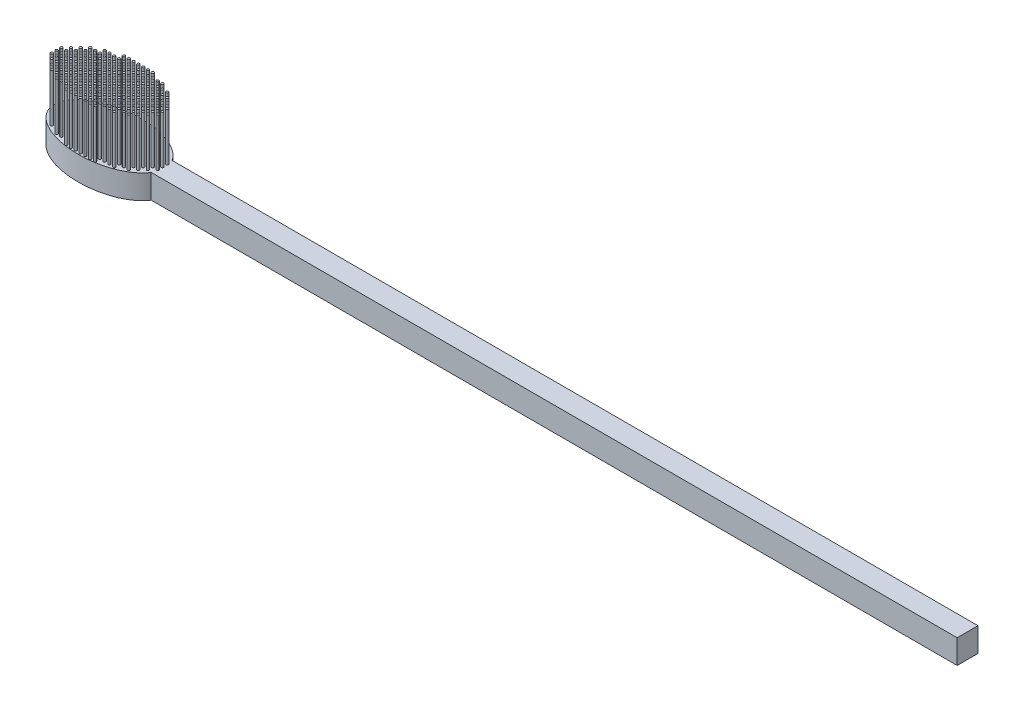
SolidWorks part; units mm, degrees
ref_plane "Front Plane" through (0, 0, 0) normal (0, 0, 1) x (1, 0, 0)
ref_plane "Top Plane" through (0, 0, 0) normal (0, 1, 0) x (1, 0, 0)
ref_plane "Right Plane" through (0, 0, 0) normal (1, 0, 0) x (0, 0, -1)
sketch "Sketch1" plane through (0, 0, 0) normal (0, 1, 0) x (1, 0, 0)
  line L0 (-11.5, 0) -> (11.5, 0) construction
  line L1 (11.5, 0) -> (178.5, 0) construction
  line L3 (10.8423, -2.1667) -> (178.5, -2.1667)
  line L5 (10.8423, 2.1667) -> (178.5, 2.1667)
  line L6 (178.5, -2.1667) -> (178.5, 2.1667)
  ellipse E0 centre (0, 0) end of major axis (11.5, 0) minor radius 6.5 (10.8423, 2.1667) -> (10.8423, -2.1667) ccw
  dimension "D1" = 13
  dimension "D2" = 23
  dimension "D3" = 190
  dimension "D4" = 4.3333
extrude "Boss-Extrude1" add sketch "Sketch1" against normal blind 5
sketch "Sketch3" plane through (0, 0, 0) normal (0, 1, 0) x (1, 0, 0)
  circle A0 centre (0, 0) radius 0.25
  dimension "D1" = 0.5
extrude "Boss-Extrude2" add sketch "Sketch3" along normal blind 10
sketch "Sketch4" plane through (0, 0, 0) normal (0, 1, 0) x (1, 0, 0)
  line L0 (0, 0) -> (11.5, 0) construction
  line L1 (0, 0) -> (0, 6.5) construction
  ellipse E0 centre (0, 0) end of major axis (11.5, 0) minor radius 6.5 construction
pattern_linear "LPattern1" count 12 spacing 1 along (1, 0, 0) count 7 spacing 1 along (0, 0, 1) skipping (4, 6), (5, 6), (6, 6), (7, 5), (7, 6), (8, 5), (8, 6), (9, 4), (9, 5), (9, 6), (10, 3), (10, 4), (10, 5), (10, 6), (11, 2), (11, 3), (11, 4), (11, 5), (11, 6) of "Boss-Extrude2"
mirror "Mirror1" about plane through (0, 0, 0) normal (0, 0, 1) of "LPattern1"
mirror "Mirror2" about plane through (0, 0, 0) normal (1, 0, 0) of "LPattern1", "Mirror1"
ref_plane "Positioning Block Plane" through (-11.5, 0, 0) normal (1, 0, 0) x (0, 0, -1)
equation "\"D4@Sketch1\"=\"D1@Sketch1\"/3"
